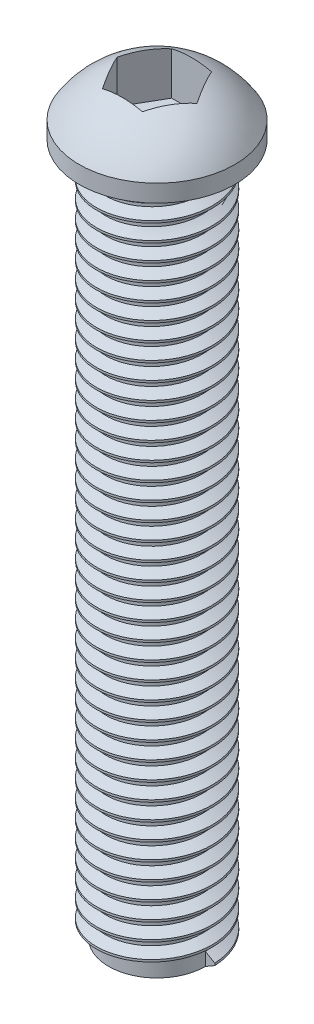
SolidWorks part; units mm, degrees
ref_plane "Front Plane" through (0, 0, 0) normal (0, 0, 1) x (1, 0, 0)
ref_plane "Top Plane" through (0, 0, 0) normal (0, 1, 0) x (1, 0, 0)
ref_plane "Right Plane" through (0, 0, 0) normal (1, 0, 0) x (0, 0, -1)
sketch "Sketch1" plane through (0, 0, 0) normal (0, 1, 0) x (1, 0, 0)
  circle A0 centre (0, 0) radius 1.4
  dimension "D1" = 2.8
extrude "Boss-Extrude1" add sketch "Sketch1" against normal blind 20
sketch "Sketch2" plane through (0, 0, 0) normal (0, 0, 1) x (1, 0, 0)
  line L0 (0, 0) -> (2.25, 0)
  line L1 (2.25, 0) -> (2.25, 0.5)
  line L2 (0, 0) -> (0, 1.75)
  arc A0 (0, 1.75) -> (2.25, 0.5) centre (0, -0.9) cw
  dimension "D1" = 2.25
  dimension "D2" = 0.5
  dimension "D3" = 1.75
revolve "Revolve1" add sketch "Sketch2" angle 360 about L2
sketch "Sketch3" plane through (0, 0, 0) normal (0, 1, 0) x (1, 0, 0)
  line L1 (1.1547, 0) -> (0.5774, 1)
  line L2 (0.5774, 1) -> (-0.5774, 1)
  line L3 (-0.5774, 1) -> (-1.1547, 0)
  line L4 (-1.1547, 0) -> (-0.5774, -1)
  line L5 (-0.5774, -1) -> (0.5774, -1)
  line L6 (0.5774, -1) -> (1.1547, 0)
  circle A0 centre (0, 0) radius 1 construction
  dimension "D1" = 2
  dimension "D2" = 1
extrude "Cut-Extrude1" cut sketch "Sketch3" against normal blind 1.5 from offset 1.75
thread "Thread2" pitch 0.5 method extrude profile "Thread Profile2" start angle 0, offset 0, length 0, pitch 0.5, diameter 2.8
ref_plane "Plane2" through (1.4, -20, 0) normal (0, 0, 1) x (1, 0, 0)
sketch "Thread Profile2" plane through (1.4, -20, 0) normal (0, 0, 1) x (1, 0, 0)
  line L0 (0, 0) -> (0, 0.5) construction
  line L1 (0, 0) -> (0.2706, 0.1562)
  line L2 (0.2706, 0.1562) -> (0.2706, 0.2187)
  line L3 (0.2706, 0.2187) -> (0, 0.375)
  line L4 (0.2706, 0.1875) -> (0, 0.1875) construction
  line L11 (0, 0) -> (0, 0.375)
  point P2 (0, 0)
  dimension "Pitch" = 0.5
  dimension "Profile_Angle" = 60
  dimension "Profile_Land" = 0.0625
  dimension "Profile_Height" = 0.2706
